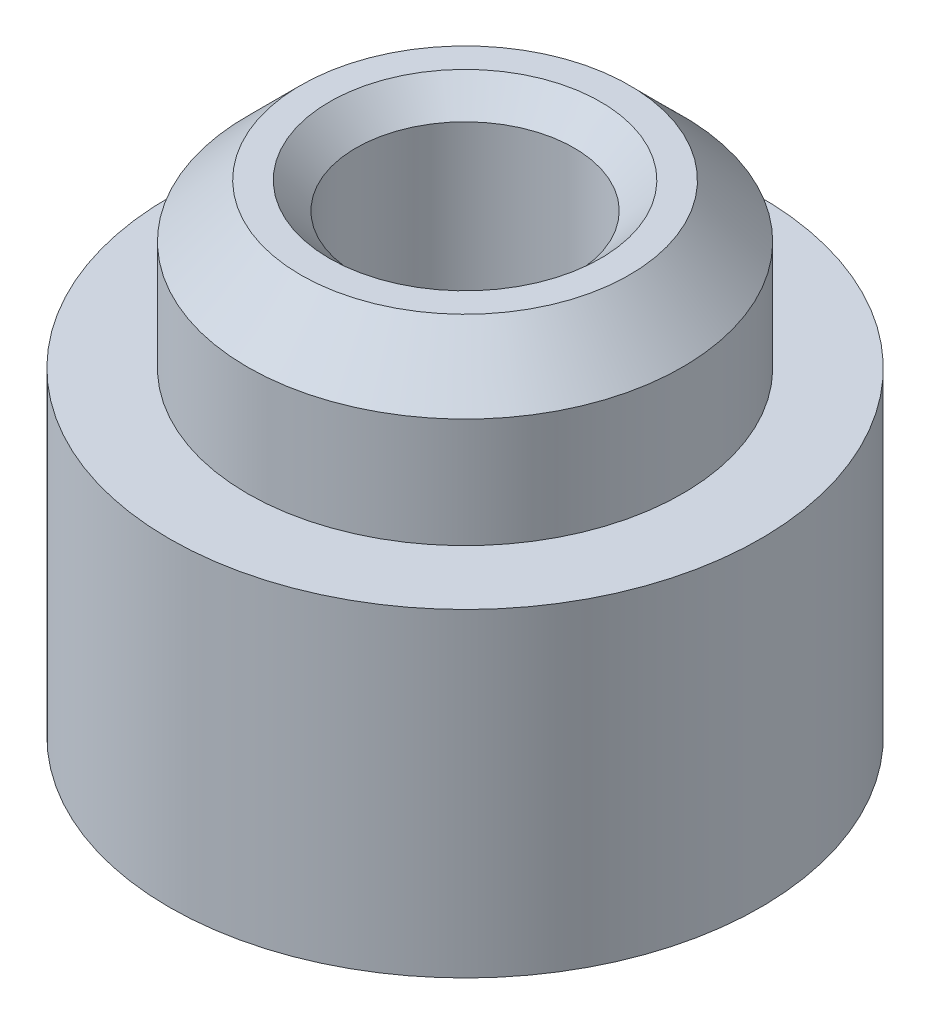
SolidWorks part; units mm, degrees
ref_plane "前视基准面" through (0, 0, 0) normal (0, 0, 1) x (1, 0, 0)
ref_plane "上视基准面" through (0, 0, 0) normal (0, 1, 0) x (1, 0, 0)
ref_plane "右视基准面" through (0, 0, 0) normal (1, 0, 0) x (0, 0, -1)
sketch "草图1" plane through (0, 0, 0) normal (0, 1, 0) x (1, 0, 0)
  circle A0 centre (0, 0) radius 2.045
  circle A1 centre (0, 0) radius 2.78
  dimension "D1" = 4.09
  dimension "D2" = 5.56
extrude "凸台-拉伸1" add sketch "草图1" along normal blind 1.53 contours A0 region at (0, 0, 0)
extrude "凸台-拉伸2" add sketch "草图1<4>" against normal blind 3 contours A0 | A1 A0 region at (0, 0, 0) region at (-2.7014, 0, 0)
sketch "草图1<4>" plane through (0, 0, 0) normal (0, 1, 0) x (1, 0, 0) same geometry as "草图1"
fillet "圆角1" radius 0.5 1 edges at (0, 1.53, 2.045) profile chamfer
hole_wizard "M2.5 螺纹孔3" positions "草图10" profile "草图11" tap size "M2.5" standard "GB" end condition through all
sketch "草图10" plane through (0, 1.53, 0) normal (0, 1, 0) x (1, 0, 0)
  point P0 (0, 0)
sketch "草图11" plane through (0, 1.53, 0) normal (1, 0, 0) x (0, 0, 1)
  line L0 (0, 0) -> (0, 4.53)
  line L1 (0, 4.53) -> (1.025, 4.53)
  line L2 (1.025, 4.53) -> (1.025, 0.25)
  line L3 (1.025, 0.25) -> (1.275, 0)
  line L5 (1.275, 0) -> (0, 0)
  line L6 (-1.025, 0.25) -> (-1.275, 0) construction
  line L11 (0, -6.35) -> (0, 107.95) construction
  dimension "通孔螺纹孔钻头直径" = 2.05
  dimension "通孔螺纹孔钻头深度" = 4.53
  dimension "近端锥形沉头孔直径" = 2.55
  dimension "近端锥形沉头孔角度" = 90
cosmetic thread "孔螺蚊线2" parameters "D2"=2.5
